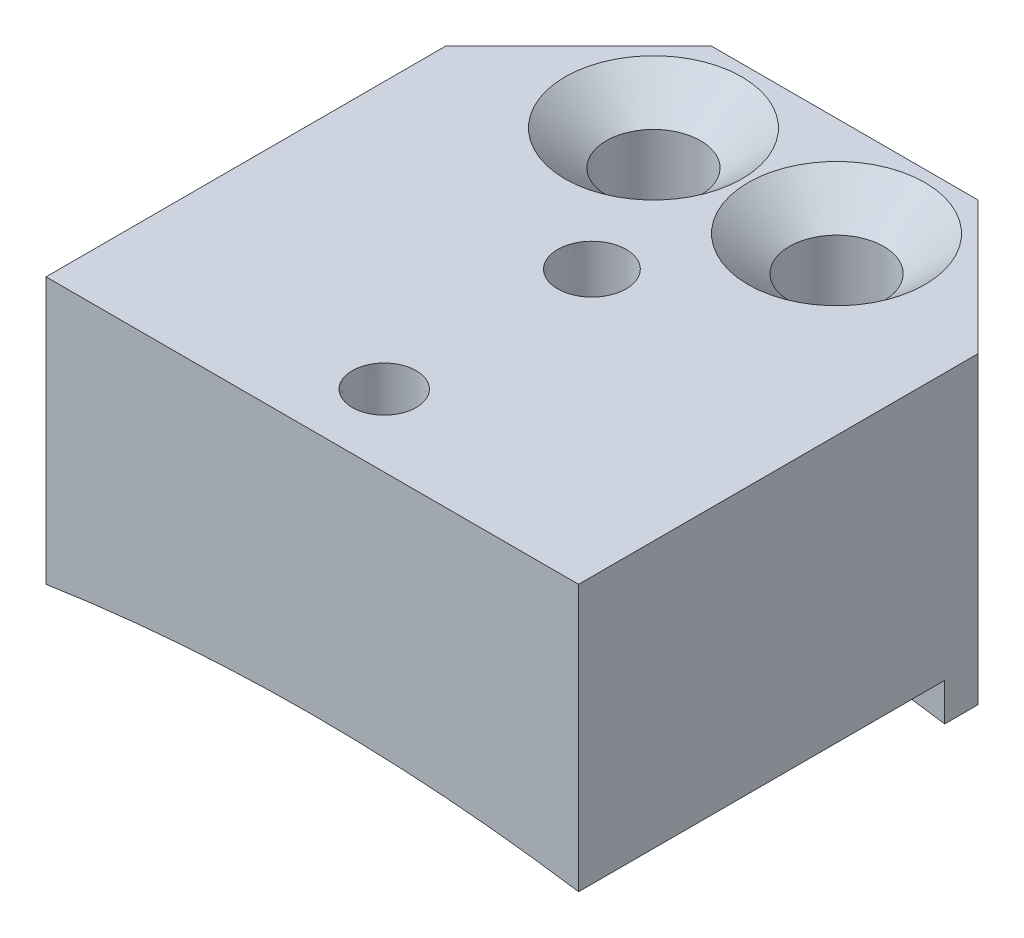
SolidWorks part; units mm, degrees
ref_plane "Front Plane" through (0, 0, 0) normal (0, 0, 1) x (1, 0, 0)
ref_plane "Top Plane" through (0, 0, 0) normal (0, 1, 0) x (1, 0, 0)
ref_plane "Right Plane" through (0, 0, 0) normal (1, 0, 0) x (0, 0, -1)
sketch "Sketch1" plane through (0, 0, 0) normal (0, 1, 0) x (1, 0, 0)
  line L0 (-28.5118, 6.4953) -> (-22.1618, 12.8453)
  line L1 (-22.1618, 12.8453) -> (-9.4618, 12.8453)
  line L2 (-28.5118, 6.4953) -> (-28.5118, -12.5547)
  line L3 (-28.5118, -12.5547) -> (-3.1118, -12.5547)
  line L4 (-3.1118, 6.4953) -> (-3.1118, -12.5547)
  line L5 (-9.4618, 12.8453) -> (-3.1118, 6.4953)
  line L6 (-15.8118, -12.5547) -> (-15.8118, 12.8453) construction
  line L8 (-3.1118, 6.4953) -> (-3.1118, 12.8453) construction
  line L9 (-3.1118, 12.8453) -> (-9.4618, 12.8453) construction
  dimension "D1" = 12.7
  dimension "D2" = 25.4
  dimension "D3" = 25.4
extrude "Boss-Extrude1" add sketch "Sketch1" along normal blind 12.7
sketch "Sketch2" plane through (0, 0, 12.5547) normal (0, 0, 1) x (1, 0, 0)
  circle A0 centre (-15.8118, -82.8523) radius 83.82
  dimension "D1" = 167.64
extrude "Cut-Extrude1" cut sketch "Sketch2" against normal through all both and the other way through all
sketch "Sketch5" plane through (0, 0, -12.8453) normal (0, 0, -1) x (-1, 0, 0)
  line L0 (3.1118, 12.7) -> (3.1118, 0) construction
  line L1 (3.1118, 12.7) -> (3.1118, 0)
  line L4 (28.5118, 12.7) -> (28.5118, 0) construction
  line L5 (28.5118, 12.7) -> (28.5118, 0)
  line L6 (28.5118, -1.7992) -> (28.5118, 0)
  line L7 (3.1118, -1.7992) -> (3.1118, 0)
  line L8 (3.1118, 12.7) -> (28.5118, 12.7)
  arc A0 (3.1118, -1.7992) -> (28.5118, -1.7992) centre (15.8118, -82.8523) cw
  arc A1 (28.5118, 0) -> (3.1118, 0) centre (15.8118, -82.8523) ccw construction
  arc A2 (28.5118, 0) -> (3.1118, 0) centre (15.8118, -82.8523) ccw construction
  dimension "D1" = 82.042
extrude "Boss-Extrude2" add sketch "Sketch5" against normal blind 7.9375
chamfer "Chamfer1" distance 6.35 angle 45 2 edges at (-28.5118, 5.4504, -12.8453) (-3.1118, 5.4504, -12.8453)
hole_wizard "CSK for #8 Flat Head Machine Screw (100)1" positions "Sketch3" profile "Sketch4" countersink size "#8" standard "ANSI Inch" end condition through all
sketch "Sketch3" plane through (0, 12.7, 0) normal (0, 1, 0) x (1, 0, 0)
  line L0 (-15.8118, 12.8453) -> (-15.8118, 3.4006) construction
  line L1 (-9.4618, 12.8453) -> (-22.1618, 12.8453) construction
  point P0 (-20.1775, 8.0828)
  point P12 (-11.4462, 8.0828)
  dimension "D1" = 4.7625
  dimension "D2" = 4.3656
sketch "Sketch4" plane through (-20.1775, 12.7, -8.0828) normal (1, 0, 0) x (0, 0, 1)
  line L0 (0, 0) -> (0, 14.4992)
  line L1 (0, 14.4992) -> (2.2479, 14.4992)
  line L2 (2.2479, 14.4992) -> (2.2479, 1.6518)
  line L3 (2.2479, 1.6518) -> (4.2164, 0)
  line L5 (4.2164, 0) -> (0, 0)
  line L6 (-2.2479, 1.6518) -> (-4.2164, 0) construction
  line L11 (0, -6.35) -> (0, 107.95) construction
  dimension "Thru Hole Dia." = 4.4958
  dimension "Thru Hole Depth" = 14.4992
  dimension "Near C'Sink Dia." = 8.4328
  dimension "Near C'Sink Angle" = 100
sketch "Sketch6" plane through (0, 12.7, 0) normal (0, 1, 0) x (1, 0, 0)
  spline S0 degree 3 poles (-15.9109, -10.6497) (-15.6088, -10.6497) (-15.4088, -10.6093) (-15.0421, -10.4569) (-14.8723, -10.3433) (-14.6614, -10.1321) (-14.5971, -10.0536) (-14.4867, -9.888) (-14.44, -9.8004) (-14.3254, -9.523) (-14.286, -9.3252) (-14.2863, -9.0237) (-14.2962, -8.9248) (-14.3351, -8.7299) (-14.3646, -8.633) (-14.4412, -8.4488) (-14.488, -8.3613) (-14.5989, -8.1955) (-14.6633, -8.1172) (-14.8743, -7.9067) (-15.0444, -7.7932) (-15.4113, -7.6415) (-15.6118, -7.6017) (-15.9102, -7.6018) (-16.0112, -7.6118) (-16.2064, -7.6508) (-16.3014, -7.6796) (-16.5784, -7.7944) (-16.7462, -7.9063) (-16.9595, -8.1198) (-17.0224, -8.1968) (-17.1327, -8.362) (-17.1804, -8.4512) (-17.2567, -8.6357) (-17.2855, -8.7307) (-17.3244, -8.9262) (-17.3342, -9.0271) (-17.3341, -9.3253) (-17.2941, -9.5259) (-17.142, -9.8926) (-17.0285, -10.0627) (-16.8176, -10.2736) (-16.7392, -10.3379) (-16.5735, -10.4485) (-16.486, -10.4953) (-16.3014, -10.5718) (-16.2047, -10.6011) (-16.0099, -10.6398) (-15.9109, -10.6497) (-15.6088, -10.6497) (-15.4088, -10.6093) knots -0.03125 -0.03125 0 0 0.0625 0.0625 0.125 0.125 0.15625 0.15625 0.1875 0.1875 0.25 0.25 0.28125 0.28125 0.3125 0.3125 0.34375 0.34375 0.375 0.375 0.4375 0.4375 0.5 0.5 0.53125 0.53125 0.5625 0.5625 0.625 0.625 0.65625 0.65625 0.6875 0.6875 0.71875 0.71875 0.75 0.75 0.8125 0.8125 0.875 0.875 0.90625 0.90625 0.9375 0.9375 0.96875 0.96875 1 1 1.0625 1.0625 1.125 only from (-15.8102, -10.6497) to (-15.8102, -10.6497) construction
  spline S1 degree 3 poles (-15.9109, -10.6497) (-15.6088, -10.6497) (-15.4088, -10.6093) (-15.0421, -10.4569) (-14.8723, -10.3433) (-14.6614, -10.1321) (-14.5971, -10.0536) (-14.4867, -9.888) (-14.44, -9.8004) (-14.3254, -9.523) (-14.286, -9.3252) (-14.2863, -9.0237) (-14.2962, -8.9248) (-14.3351, -8.7299) (-14.3646, -8.633) (-14.4412, -8.4488) (-14.488, -8.3613) (-14.5989, -8.1955) (-14.6633, -8.1172) (-14.8743, -7.9067) (-15.0444, -7.7932) (-15.4113, -7.6415) (-15.6118, -7.6017) (-15.9102, -7.6018) (-16.0112, -7.6118) (-16.2064, -7.6508) (-16.3014, -7.6796) (-16.5784, -7.7944) (-16.7462, -7.9063) (-16.9595, -8.1198) (-17.0224, -8.1968) (-17.1327, -8.362) (-17.1804, -8.4512) (-17.2567, -8.6357) (-17.2855, -8.7307) (-17.3244, -8.9262) (-17.3342, -9.0271) (-17.3341, -9.3253) (-17.2941, -9.5259) (-17.142, -9.8926) (-17.0285, -10.0627) (-16.8176, -10.2736) (-16.7392, -10.3379) (-16.5735, -10.4485) (-16.486, -10.4953) (-16.3014, -10.5718) (-16.2047, -10.6011) (-16.0099, -10.6398) (-15.9109, -10.6497) (-15.6088, -10.6497) (-15.4088, -10.6093) knots -0.03125 -0.03125 0 0 0.0625 0.0625 0.125 0.125 0.15625 0.15625 0.1875 0.1875 0.25 0.25 0.28125 0.28125 0.3125 0.3125 0.34375 0.34375 0.375 0.375 0.4375 0.4375 0.5 0.5 0.53125 0.53125 0.5625 0.5625 0.625 0.625 0.65625 0.65625 0.6875 0.6875 0.71875 0.71875 0.75 0.75 0.8125 0.8125 0.875 0.875 0.90625 0.90625 0.9375 0.9375 0.96875 0.96875 1 1 1.0625 1.0625 1.125 only from (-15.8102, -10.6497) to (-15.8102, -10.6497)
  spline S2 degree 3 poles (-17.442, 0.8881) (-17.442, 0.5646) (-17.3987, 0.3504) (-17.2355, -0.0422) (-17.1139, -0.2241) (-16.8877, -0.4499) (-16.8036, -0.5187) (-16.6263, -0.6369) (-16.5325, -0.687) (-16.2355, -0.8097) (-16.0236, -0.8519) (-15.7008, -0.8516) (-15.5949, -0.8409) (-15.3862, -0.7993) (-15.2825, -0.7677) (-15.0851, -0.6857) (-14.9915, -0.6355) (-14.814, -0.5168) (-14.7301, -0.4479) (-14.5047, -0.222) (-14.3832, -0.0397) (-14.2207, 0.3532) (-14.178, 0.5678) (-14.1782, 0.8874) (-14.1889, 0.9955) (-14.2306, 1.2046) (-14.2615, 1.3063) (-14.3435, 1.5041) (-14.3946, 1.5994) (-14.5128, 1.7761) (-14.5805, 1.8587) (-14.7329, 2.0109) (-14.8153, 2.0784) (-14.9922, 2.1965) (-15.0878, 2.2476) (-15.2854, 2.3293) (-15.3871, 2.3601) (-15.5964, 2.4017) (-15.7045, 2.4123) (-16.0238, 2.4121) (-16.2385, 2.3692) (-16.6313, 2.2065) (-16.8134, 2.0849) (-17.0392, 1.8591) (-17.1081, 1.7751) (-17.2266, 1.5977) (-17.2767, 1.5039) (-17.3586, 1.3063) (-17.39, 1.2027) (-17.4314, 0.9941) (-17.442, 0.8881) (-17.442, 0.5646) (-17.3987, 0.3504) knots -0.03125 -0.03125 0 0 0.0625 0.0625 0.125 0.125 0.15625 0.15625 0.1875 0.1875 0.25 0.25 0.28125 0.28125 0.3125 0.3125 0.34375 0.34375 0.375 0.375 0.4375 0.4375 0.5 0.5 0.53125 0.53125 0.5625 0.5625 0.59375 0.59375 0.625 0.625 0.65625 0.65625 0.6875 0.6875 0.71875 0.71875 0.75 0.75 0.8125 0.8125 0.875 0.875 0.90625 0.90625 0.9375 0.9375 0.96875 0.96875 1 1 1.0625 1.0625 1.125 only from (-17.442, 0.7803) to (-17.442, 0.7803) construction
  spline S3 degree 3 poles (-17.442, 0.8881) (-17.442, 0.5646) (-17.3987, 0.3504) (-17.2355, -0.0422) (-17.1139, -0.2241) (-16.8877, -0.4499) (-16.8036, -0.5187) (-16.6263, -0.6369) (-16.5325, -0.687) (-16.2355, -0.8097) (-16.0236, -0.8519) (-15.7008, -0.8516) (-15.5949, -0.8409) (-15.3862, -0.7993) (-15.2825, -0.7677) (-15.0851, -0.6857) (-14.9915, -0.6355) (-14.814, -0.5168) (-14.7301, -0.4479) (-14.5047, -0.222) (-14.3832, -0.0397) (-14.2207, 0.3532) (-14.178, 0.5678) (-14.1782, 0.8874) (-14.1889, 0.9955) (-14.2306, 1.2046) (-14.2615, 1.3063) (-14.3435, 1.5041) (-14.3946, 1.5994) (-14.5128, 1.7761) (-14.5805, 1.8587) (-14.7329, 2.0109) (-14.8153, 2.0784) (-14.9922, 2.1965) (-15.0878, 2.2476) (-15.2854, 2.3293) (-15.3871, 2.3601) (-15.5964, 2.4017) (-15.7045, 2.4123) (-16.0238, 2.4121) (-16.2385, 2.3692) (-16.6313, 2.2065) (-16.8134, 2.0849) (-17.0392, 1.8591) (-17.1081, 1.7751) (-17.2266, 1.5977) (-17.2767, 1.5039) (-17.3586, 1.3063) (-17.39, 1.2027) (-17.4314, 0.9941) (-17.442, 0.8881) (-17.442, 0.5646) (-17.3987, 0.3504) knots -0.03125 -0.03125 0 0 0.0625 0.0625 0.125 0.125 0.15625 0.15625 0.1875 0.1875 0.25 0.25 0.28125 0.28125 0.3125 0.3125 0.34375 0.34375 0.375 0.375 0.4375 0.4375 0.5 0.5 0.53125 0.53125 0.5625 0.5625 0.59375 0.59375 0.625 0.625 0.65625 0.65625 0.6875 0.6875 0.71875 0.71875 0.75 0.75 0.8125 0.8125 0.875 0.875 0.90625 0.90625 0.9375 0.9375 0.96875 0.96875 1 1 1.0625 1.0625 1.125 only from (-17.442, 0.7803) to (-17.442, 0.7803)
extrude "Cut-Extrude2" cut sketch "Sketch6" against normal through all
